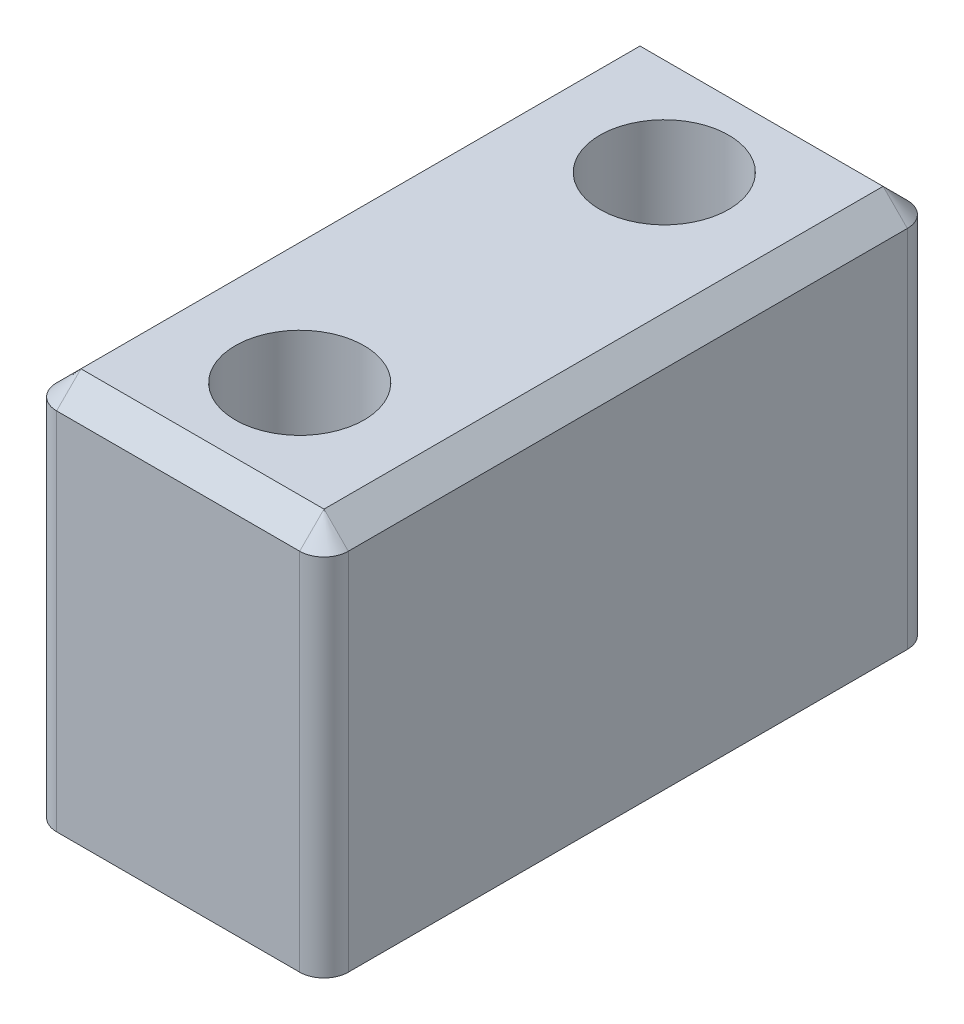
SolidWorks part; units mm, degrees
ref_plane "Front Plane" through (0, 0, 0) normal (0, 0, 1) x (1, 0, 0)
ref_plane "Top Plane" through (0, 0, 0) normal (0, 1, 0) x (1, 0, 0)
ref_plane "Right Plane" through (0, 0, 0) normal (1, 0, 0) x (0, 0, -1)
sketch "Sketch1" plane through (0, 0, 0) normal (0, 1, 0) x (1, 0, 0)
  line L0 (0, 7.5) -> (0, -7.5) construction
  line L1 (-6, 12.5) -> (6, 12.5)
  line L2 (-6, 12.5) -> (-6, -12.5)
  line L3 (-6, -12.5) -> (6, -12.5)
  line L4 (6, 12.5) -> (6, -12.5)
  line L5 (-6, 12.5) -> (6, -12.5) construction
  line L6 (-6, -12.5) -> (6, 12.5) construction
  circle A0 centre (0, 7.5) radius 2.65
  circle A1 centre (0, -7.5) radius 2.65
  point P0 (0, 0)
  dimension "D2" = 5.3
  dimension "D3" = 15
  dimension "D5" = 5.3
  dimension "D1" = 25
  dimension "D4" = 12
extrude "Boss-Extrude1" add sketch "Sketch1" along normal mid plane 16
fillet "Fillet1" radius 1 4 edges at (-6, 0, 12.5) (-6, 0, -12.5) (6, 0, -12.5) (6, 0, 12.5)
chamfer "Chamfer1" distance 1 angle 45 8 edges at (0, 8, -12.5) (-5.7071, 8, -12.2071) (5.7071, 8, -12.2071) (-6, 8, 0) (6, 8, 0) (-5.7071, 8, 12.2071) (5.7071, 8, 12.2071) (0, 8, 12.5)
